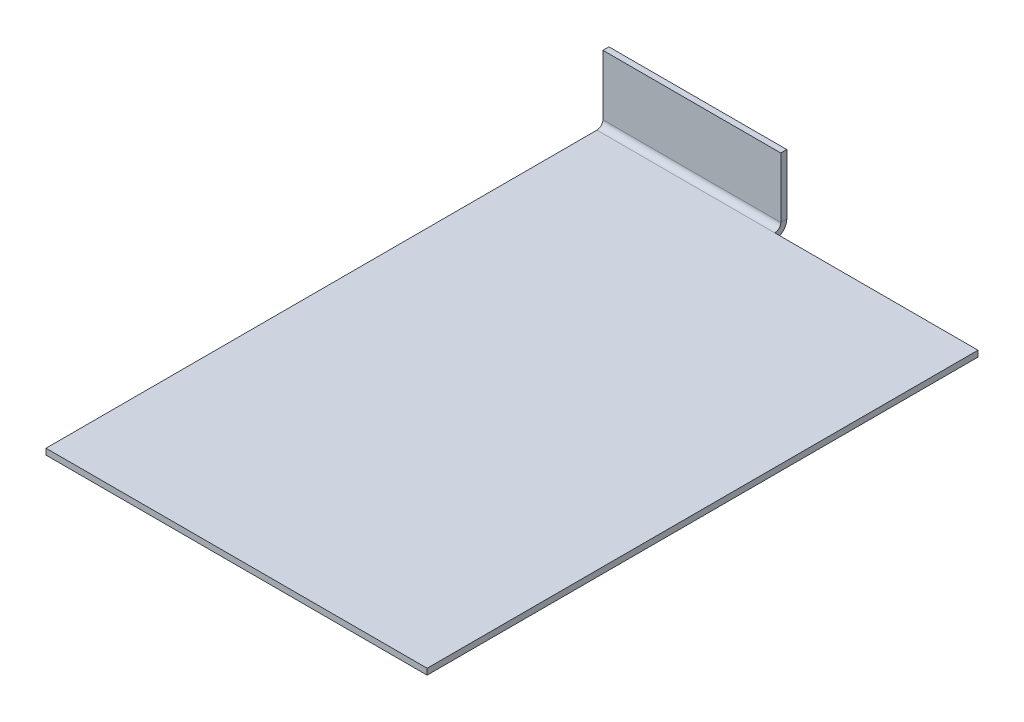
SolidWorks part; units mm, degrees
note: The reader was unsure of these and kept them because the rebuilt part matched: flange length of "Edge-Flange1".
material "6061-T6 (SS)"
ref_plane "X-Y Datum" through (0, 0, 0) normal (0, 0, 1) x (1, 0, 0)
ref_plane "X-Z Datum" through (0, 0, 0) normal (0, 1, 0) x (1, 0, 0)
ref_plane "Y-Z Datum" through (0, 0, 0) normal (1, 0, 0) x (0, 0, -1)
sketch "Sketch1" plane through (0, 0, 0) normal (0, 1, 0) x (1, 0, 0)
  line L1 (0, 0) -> (201.2086, 0)
  line L2 (0, 0) -> (0, 290.83)
  line L3 (0, 290.83) -> (201.2086, 290.83)
  line L4 (201.2086, 0) -> (201.2086, 290.83)
base flange "Base-Flange1" sketch "Sketch1" thickness 3.175 reverse thickness direction no parameters "D1"=3.175
edge flange "Edge-Flange1" sketch "Sketch8" flange angle 90 flange length 38.1 flange position bend outside bend radius 3.175 thickness 3.175 relief rectangular parameters "D6"=10
sketch "Sketch8" plane through (0, 0, -290.83) normal (0, 0, -1) x (-1, 0, 0)
  line L0 (-201.2086, 0) -> (0, 0) construction
  line L1 (-93.9215, 0) -> (0, 0)
  line L3 (-93.9215, 34.925) -> (0, 34.925)
  line L4 (0, 34.925) -> (0, 0)
  line L9 (-93.9215, 34.925) -> (-93.9215, 0)
bend "EdgeBend1" bend radius 3.175 bend angle 90 parameters "D5"=1
sketch "Bend-Lines1" [suppressed] plane through (0, 0, 0) normal (0, 1, 0) x (1, 0, 0)
sketch "Bounding-Box1" [suppressed] plane through (0, 0, 0) normal (0, 1, 0) x (1, 0, 0)
sheet metal parameters "Sheet-Metal1" thickness 3.175 parameters "D1"=3.175
flat pattern "Flat-Pattern1" [suppressed]
sketch "Bend-Lines2" plane through (0, 0, 0) normal (0, 1, 0) x (1, 0, 0)
sketch3d "Bounding-Box2" [suppressed]
  line L0 (0, 0, 0) -> (0, 290.83, 0) construction
  line L1 (-201.2086, 0, 0) -> (-201.2086, 290.83, 0) construction
  line L2 (0, 0, 0) -> (-201.2086, 0, 0) construction
  line L3 (0, 290.83, 0) -> (-201.2086, 290.83, 0) construction
sheet metal parameters "Sheet-Metal2" thickness 3.175 parameters "D1"=3.175
flat pattern "Flat-Pattern1"
sketch "Bend-Lines2" plane through (0, 0, 0) normal (0, 1, 0) x (1, 0, 0)
  line L0 (93.9215, 294.5705) -> (0, 294.5705) construction
  line L1 (93.9215, 294.5705) -> (0, 294.5705) construction
sketch3d "Bounding-Box2" [suppressed]
  line L0 (0, 0, 0) -> (0, 330.0609, 0) construction
  line L1 (201.2086, 0, 0) -> (201.2086, 330.0609, 0) construction
  line L2 (0, 0, 0) -> (201.2086, 0, 0) construction
  line L3 (0, 330.0609, 0) -> (201.2086, 330.0609, 0) construction
bend of the flat pattern "Flatten-<EdgeBend1>1"
